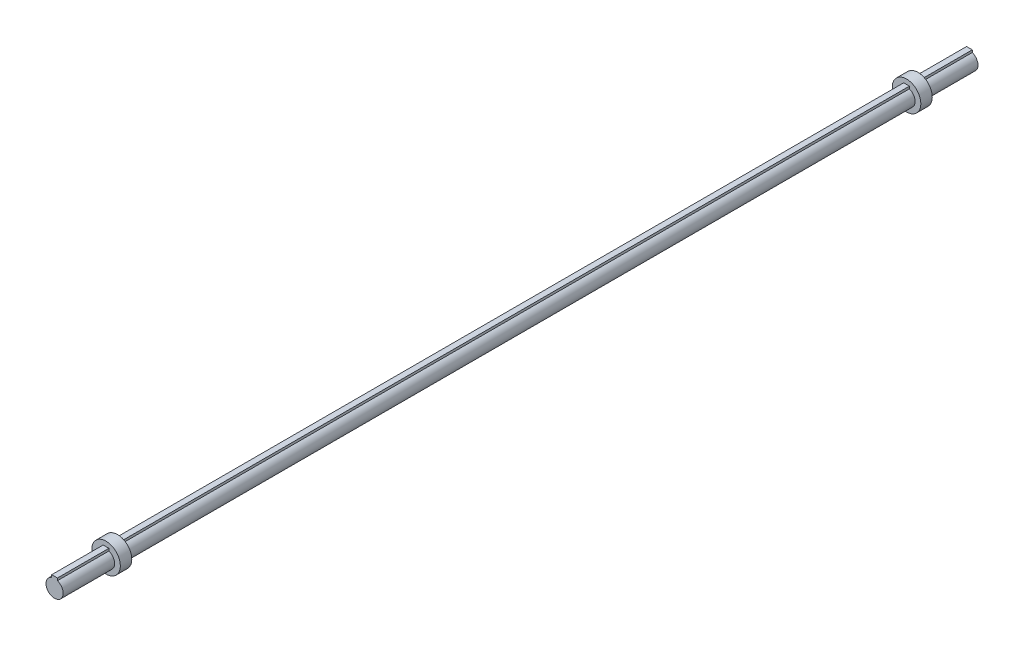
SolidWorks part; units mm, degrees
ref_plane "Front Plane" through (0, 0, 0) normal (0, 0, 1) x (1, 0, 0)
ref_plane "Top Plane" through (0, 0, 0) normal (0, 1, 0) x (1, 0, 0)
ref_plane "Right Plane" through (0, 0, 0) normal (1, 0, 0) x (0, 0, -1)
sketch "Sketch1" plane through (0, 0, 0) normal (0, 0, 1) x (1, 0, 0)
  line L0 (-5, 12.4921) -> (-5, 16.65)
  line L1 (5, 16.65) -> (5, 12.4921)
  line L2 (-5, 16.65) -> (5, 16.65)
  arc A0 (-5, 12.4921) -> (5, 12.4921) centre (0, -1.65) ccw
  dimension "D1" = 15
  dimension "D2" = 10
  dimension "D3" = 18.3
  dimension "D4" = 5
extrude "Boss-Extrude1" add sketch "Sketch1" along normal mid plane 1600
ref_plane "Plane1" through (0, 0, 710) normal (0, 0, 1) x (1, 0, 0)
sketch "Sketch2" plane through (0, 0, 710) normal (0, 0, 1) x (1, 0, 0)
  circle A0 centre (0, 0) radius 25
  dimension "D1" = 50
extrude "Boss-Extrude2" add sketch "Sketch2" against normal blind 20
mirror "Mirror1" about plane through (0, 0, 0) normal (0, 0, 1) of "Boss-Extrude2"
ref_axis "Axis1" through (0, -1.65, 690) along (0, 0, -1)
